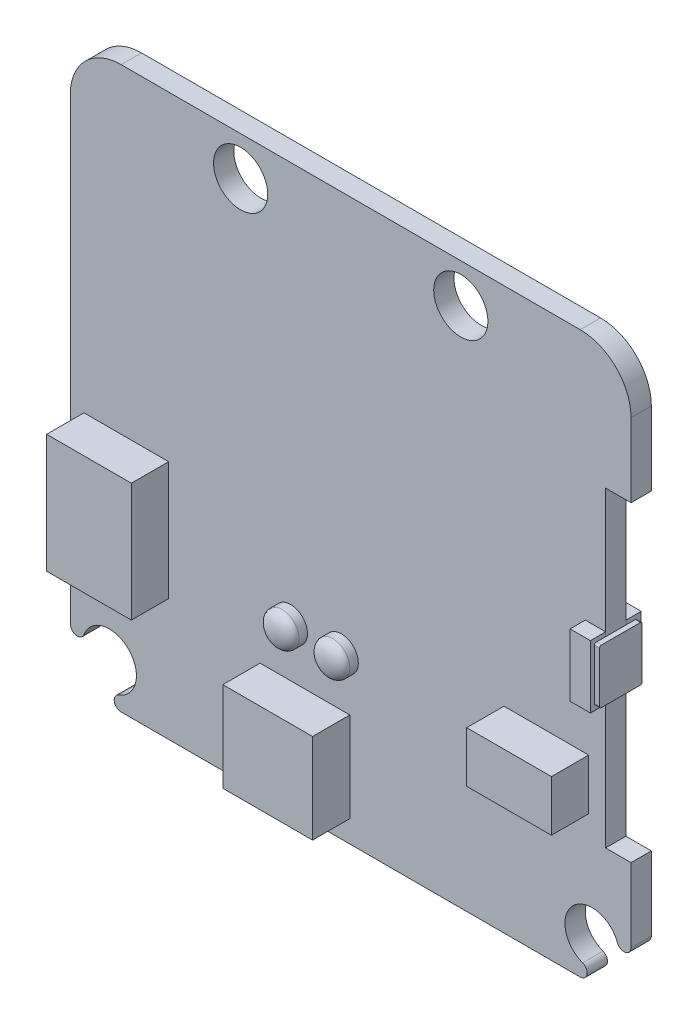
SolidWorks part; units mm, degrees
material "АМг"
ref_plane "Спереди" through (0, 0, 0) normal (0, 0, 1) x (1, 0, 0)
ref_plane "Сверху" through (0, 0, 0) normal (0, 1, 0) x (1, 0, 0)
ref_plane "Справа" through (0, 0, 0) normal (1, 0, 0) x (0, 0, -1)
sketch "Эскиз1" plane through (0, 0, 0) normal (0, 0, 1) x (1, 0, 0)
  line L0 (0, 0) -> (0, 16.55) construction
  line L1 (-13.55, -16.55) -> (13.55, -16.55)
  line L2 (-16.55, -13.55) -> (-16.55, 13.55)
  line L3 (-13.55, 16.55) -> (13.55, 16.55)
  line L4 (16.55, -13.55) -> (16.55, 13.55)
  line L5 (-16.55, -16.55) -> (16.55, 16.55) construction
  line L6 (-16.55, 16.55) -> (16.55, -16.55) construction
  line L8 (0, 0) -> (16.55, 0) construction
  arc A0 (-13.55, -16.55) -> (-16.55, -13.55) centre (-13.55, -13.55) cw
  arc A1 (13.55, -16.55) -> (16.55, -13.55) centre (13.55, -13.55) ccw
  arc A2 (13.55, 16.55) -> (16.55, 13.55) centre (13.55, 13.55) cw
  arc A3 (-16.55, 13.55) -> (-13.55, 16.55) centre (-13.55, 13.55) cw
  point P0 (0, 0)
  dimension "D2" = 3
  dimension "D1" = 33.1
extrude "Бобышка-Вытянуть1" add sketch "Эскиз1" along normal blind 1.2
sketch "Эскиз2" plane through (0, 0, 1.2) normal (0, 0, 1) x (1, 0, 0)
  line L0 (0, 0) -> (0, 16.55) construction
  line L1 (0, 0) -> (0, 16.55) construction
  line L2 (-13.55, 16.55) -> (13.55, 16.55) construction
  line L3 (0, 0) -> (16.55, 0) construction
  line L4 (-6.5, 15.85) -> (-6.5, 16.55) construction
  line L5 (-16.55, -16.55) -> (16.55, 16.55) construction
  line L6 (-16.55, -13.55) -> (-16.55, 13.55) construction
  line L7 (-13.55, -16.55) -> (13.55, -16.55) construction
  circle A0 centre (-6.5, 14.25) radius 1.6
  arc A1 (-13.6936, -15.7501) -> (-15.7501, -13.6936) centre (-14.25, -14.25) ccw
  circle A2 centre (6.5, 14.25) radius 1.6
  arc A3 (13.6936, -15.7501) -> (15.7501, -13.6936) centre (14.25, -14.25) cw
  arc A4 (-15.7501, -13.6936) -> (-16.55, -13.55) centre (-16.1372, -13.55) cw
  arc A5 (-13.6936, -15.7501) -> (-13.55, -16.55) centre (-13.55, -16.1372) ccw
  arc A6 (-16.55, -13.55) -> (-13.55, -16.55) centre (-13.55, -13.55) ccw construction
  arc A7 (-16.55, -13.55) -> (-13.55, -16.55) centre (-13.55, -13.55) ccw
  arc A8 (15.7501, -13.6936) -> (16.55, -13.55) centre (16.1372, -13.55) ccw
  arc A9 (16.55, -13.55) -> (13.55, -16.55) centre (13.55, -13.55) cw
  arc A10 (13.6936, -15.7501) -> (13.55, -16.55) centre (13.55, -16.1372) cw
  dimension "D1" = 3.2
  dimension "D2" = 13
  dimension "D3" = 2.3
  dimension "D4" = 14.25
  dimension "D5" = 2.3
extrude "Вырез-Вытянуть1" cut sketch "Эскиз2" against normal blind 1.2
sketch "Эскиз3" plane through (0, 0, 1.2) normal (0, 0, 1) x (1, 0, 0)
  line L0 (16.55, -13.55) -> (16.55, 13.55) construction
  line L1 (16.55, 9.2) -> (15.05, 9.2)
  line L2 (16.55, 9.2) -> (16.55, -9.2)
  line L3 (16.55, -9.2) -> (15.05, -9.2)
  line L4 (15.05, 9.2) -> (15.05, -9.2)
  line L5 (0, 0) -> (15.05, 0) construction
  dimension "D1" = 18.4
  dimension "D2" = 1.5
extrude "Вырез-Вытянуть2" cut sketch "Эскиз3" against normal blind 1.2
sketch "Эскиз4" plane through (0, 0, 1.2) normal (0, 0, 1) x (1, 0, 0)
  line L0 (15.05, 9.2) -> (15.05, -9.2) construction
  line L1 (15.05, 1.85) -> (13.85, 1.85)
  line L2 (15.05, 1.85) -> (15.05, -1.85)
  line L3 (15.05, -1.85) -> (13.85, -1.85)
  line L4 (13.85, 1.85) -> (13.85, -1.85)
  line L5 (0, 0) -> (13.85, 0) construction
  dimension "D1" = 3.7
  dimension "D2" = 1.2
extrude "Бобышка-Вытянуть2" add sketch "Эскиз4" along normal blind 0.9 and the other way blind 2.1 separate body
sketch "Эскиз5" plane through (15.05, 0, 0) normal (1, 0, 0) x (0, 0, -1)
  line L0 (0.55, 1.6) -> (-1.75, 1.6)
  line L1 (-1.85, 1.5) -> (-1.85, -1.5)
  line L2 (-1.75, -1.6) -> (0.55, -1.6)
  line L3 (0.65, -1.5) -> (0.65, 1.5)
  line L4 (0.9, 1.85) -> (-2.1, 1.85)
  line L5 (-2.1, 1.85) -> (-2.1, -1.85)
  line L6 (-2.1, -1.85) -> (0.9, -1.85)
  line L7 (0.9, -1.85) -> (0.9, 1.85)
  line L8 (0.9, 1.85) -> (-2.1, 1.85) construction
  line L9 (-2.1, 1.85) -> (-2.1, -1.85) construction
  line L10 (-2.1, -1.85) -> (0.9, -1.85) construction
  line L11 (0.9, -1.85) -> (0.9, 1.85) construction
  line L12 (0.65, 1.6) -> (-1.85, 1.6) construction
  line L13 (-1.85, 1.6) -> (-1.85, -1.6) construction
  line L14 (-1.85, -1.6) -> (0.65, -1.6) construction
  line L15 (0.65, -1.6) -> (0.65, 1.6) construction
  arc A0 (-1.75, 1.6) -> (-1.85, 1.5) centre (-1.75, 1.5) ccw
  arc A1 (-1.85, -1.5) -> (-1.75, -1.6) centre (-1.75, -1.5) ccw
  arc A2 (0.55, -1.6) -> (0.65, -1.5) centre (0.55, -1.5) ccw
  arc A3 (0.55, 1.6) -> (0.65, 1.5) centre (0.55, 1.5) cw
  dimension "D3" = 0.1
  dimension "D1" = 0
  dimension "D2" = 0.25
extrude "Бобышка-Вытянуть3" add sketch "Эскиз5" along normal blind 0.3 and the other way blind 0.5 separate body
sketch "Эскиз6" plane through (0, 0, 1.2) normal (0, 0, 1) x (1, 0, 0)
  line L0 (-16.55, 13.55) -> (-16.55, -13.55) construction
  line L1 (-5.35, -9.95) -> (-0.05, -9.95)
  line L2 (-5.35, -9.95) -> (-5.35, -15.25)
  line L3 (-5.35, -15.25) -> (-0.05, -15.25)
  line L4 (-0.05, -9.95) -> (-0.05, -15.25)
  line L5 (-13.55, -16.55) -> (13.55, -16.55) construction
  line L6 (15.05, 9.2) -> (15.05, -9.2) construction
  line L7 (-10.75, -9.35) -> (-15.75, -9.35)
  line L8 (-10.75, -9.35) -> (-10.75, -2.35)
  line L9 (-10.75, -2.35) -> (-15.75, -2.35)
  line L10 (-15.75, -9.35) -> (-15.75, -2.35)
  line L11 (14.05, -7.95) -> (9.05, -7.95)
  line L12 (14.05, -7.95) -> (14.05, -4.95)
  line L13 (14.05, -4.95) -> (9.05, -4.95)
  line L14 (9.05, -7.95) -> (9.05, -4.95)
  dimension "D1" = 5.3
  dimension "D2" = 16.5
  dimension "D3" = 6.6
  dimension "D4" = 5
  dimension "D5" = 7
  dimension "D6" = 7.2
  dimension "D7" = 0.8
  dimension "D8" = 11.6
  dimension "D9" = 3
  dimension "D10" = 6
  dimension "D11" = 5
extrude "Бобышка-Вытянуть4" add sketch "Эскиз6" along normal blind 2.2 separate body
sketch "Эскиз7" plane through (0, 0, 1.2) normal (0, 0, 1) x (1, 0, 0)
  line L0 (-13.55, -16.55) -> (13.55, -16.55) construction
  line L1 (-16.55, 13.55) -> (-16.55, -13.55) construction
  circle A0 centre (-3.55, -7.05) radius 1
  circle A1 centre (-0.55, -7.05) radius 1
  dimension "D1" = 9.5
  dimension "D2" = 2
  dimension "D4" = 13
  dimension "D3" = 3
extrude "Бобышка-Вытянуть5" add sketch "Эскиз7" along normal blind 0.5 separate body
dome "Купол1" faces to dome 1 distance 0.5 reverse direction no elliptical dome yes face at (0.45, -7.05, 1.7) parameters "D1"=0.5
dome "Купол2" faces to dome 1 distance 0.5 reverse direction no elliptical dome yes face at (-2.55, -7.05, 1.7) parameters "D1"=0.5
